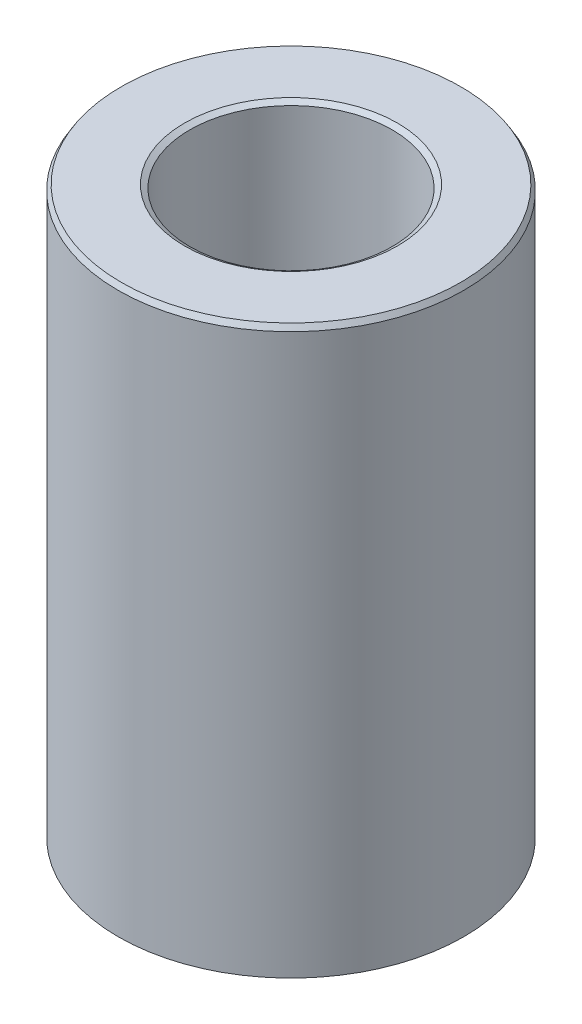
SolidWorks part; units mm, degrees
ref_plane "Front Plane" through (0, 0, 0) normal (0, 0, 1) x (1, 0, 0)
ref_plane "Top Plane" through (0, 0, 0) normal (0, 1, 0) x (1, 0, 0)
ref_plane "Right Plane" through (0, 0, 0) normal (1, 0, 0) x (0, 0, -1)
sketch "Sketch1" plane through (0, 0, 0) normal (0, 1, 0) x (1, 0, 0)
  circle A0 centre (0, 0) radius 60
  dimension "SLEEVE_OD" = 120
extrude "Boss-Extrude1" add sketch "Sketch1" along normal blind 197.2738
sketch "Sketch2" plane through (0, 0, 0) normal (0, 1, 0) x (1, 0, 0)
  circle A0 centre (0, 0) radius 35.1389
  dimension "BORE_D" = 70.2779
extrude "Cut-Extrude1" cut sketch "Sketch2" along normal through all
chamfer "Chamfer1" distance 1.8317 angle 31.219 4 edges at (0, 197.2738, 35.1389) (0, 0, 35.1389) (0, 0, 60) (0, 197.2738, 60) first distance on face at (0, 197.2738, 35.1389) first distance on face at (0, 0, 35.1389) first distance on face at (0, 197.2738, 60)
